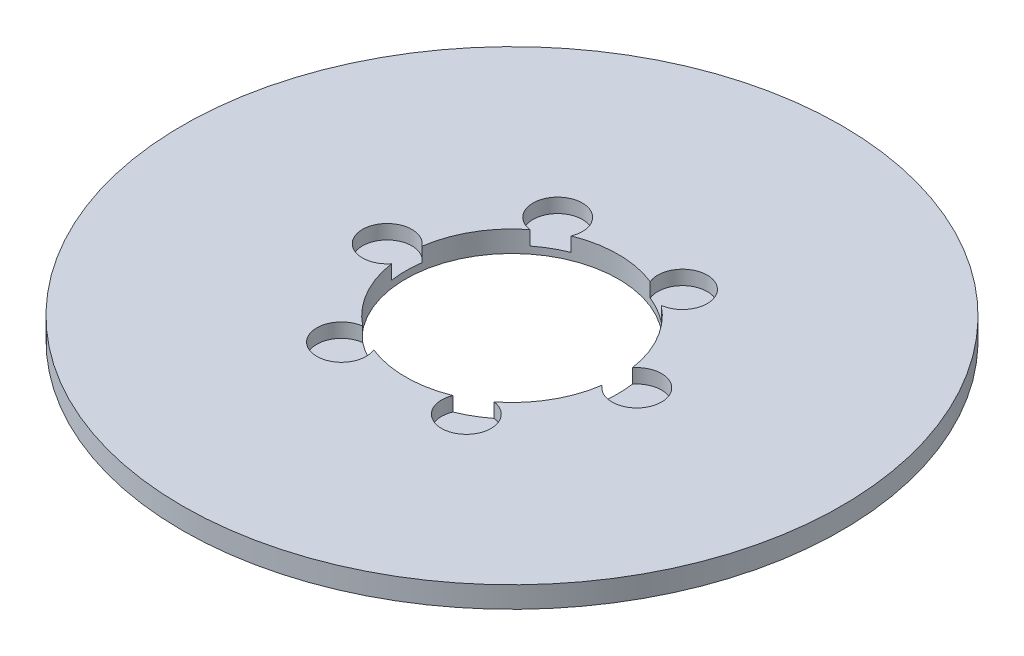
SolidWorks part; units mm, degrees
ref_plane "Front Plane" through (0, 0, 0) normal (0, 0, 1) x (1, 0, 0)
ref_plane "Top Plane" through (0, 0, 0) normal (0, 1, 0) x (1, 0, 0)
ref_plane "Right Plane" through (0, 0, 0) normal (1, 0, 0) x (0, 0, -1)
sketch "Sketch1" plane through (0, 0, 0) normal (0, 1, 0) x (1, 0, 0)
  circle A0 centre (0, 0) radius 77.5
  dimension "FLANGE_OD" = 155
extrude "Boss-Extrude1" add sketch "Sketch1" along normal blind 5
sketch "Sketch2" plane through (0, 0, 0) normal (0, 1, 0) x (1, 0, 0)
  circle A0 centre (0, 0) radius 25
  dimension "BORE_D" = 50
extrude "Cut-Extrude1" cut sketch "Sketch2" along normal through all
sketch "Sketch3" plane through (0, 5, 0) normal (0, 1, 0) x (1, 0, 0)
  circle A0 centre (0, 0) radius 29.3506 construction
  circle A1 centre (-29.3506, 0) radius 5.8168
  dimension "BOLT_D" = 11.6336
  dimension "BOLT_PCD" = 58.7012
extrude "Cut-Extrude2" cut sketch "Sketch3" against normal blind 3.3562
pattern_circular "CirPattern1" count 6 over 360 about axis through (0, 0, 0) along (0, 1, 0) of "Cut-Extrude2"
